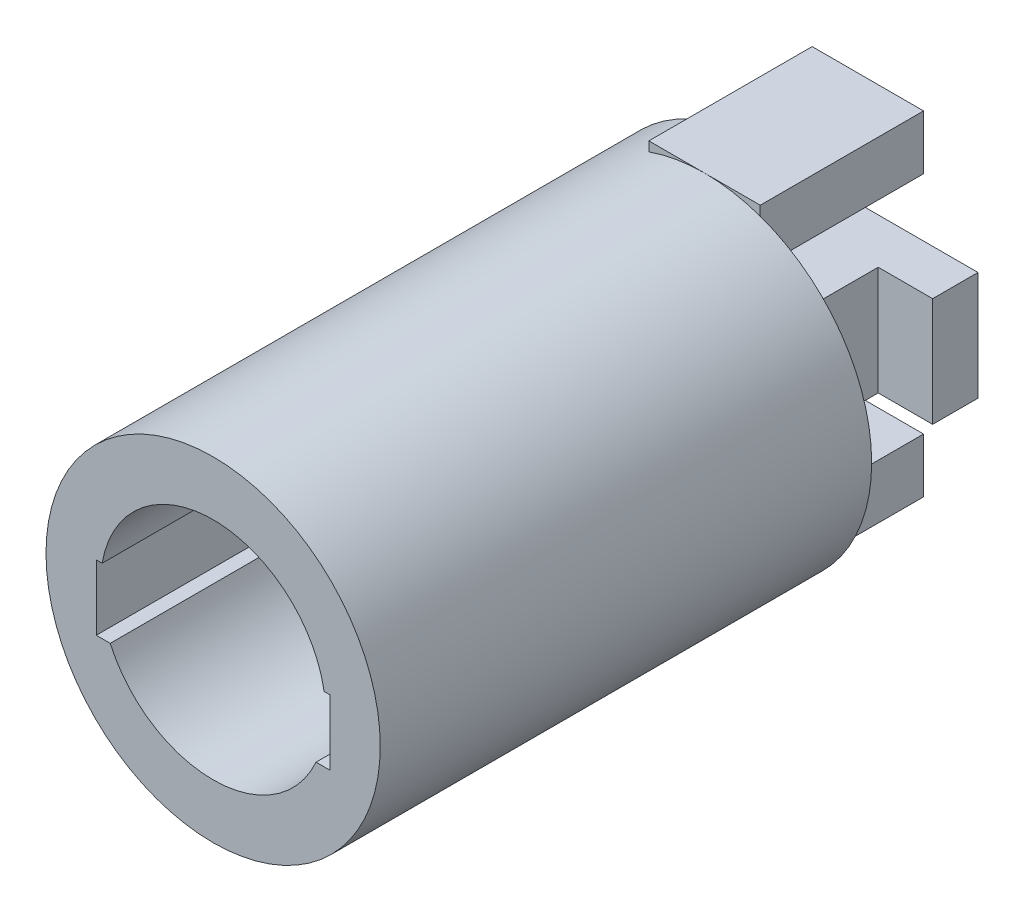
SolidWorks part; units mm, degrees
ref_plane "Front Plane" through (0, 0, 0) normal (0, 0, 1) x (1, 0, 0)
ref_plane "Top Plane" through (0, 0, 0) normal (0, 1, 0) x (1, 0, 0)
ref_plane "Right Plane" through (0, 0, 0) normal (1, 0, 0) x (0, 0, -1)
ref_plane "Plane6" through (0, 0, 0) normal (0, 0, 1) x (1, 0, 0)
sketch "Sketch9" plane through (0, 0, 0) normal (0, 0, 1) x (1, 0, 0)
  line L0 (17.9123, -8.844) -> (17.9123, 0.366)
  line L1 (21.1323, -4.604) -> (14.6923, -4.604) construction
  line L5 (14.6923, -3.704) -> (21.1323, -3.704)
  line L6 (14.6923, -3.704) -> (14.6923, -5.504)
  line L7 (14.6923, -5.504) -> (21.1323, -5.504)
  line L8 (21.1323, -3.704) -> (21.1323, -5.504)
  line L10 (17.9123, -5.504) -> (17.9123, -3.704) construction
  circle A0 centre (17.9123, -4.239) radius 4.605
  circle A1 centre (17.9123, -4.239) radius 3.105
  point P4 (0, 0)
  point P5 (0, 0)
  point P6 (17.9123, -12.5328)
  point P9 (17.9123, -4.604)
  dimension "D1" = 6.21
  dimension "D8" = 1.5
  dimension "D3" = 0.9
  dimension "D4" = 0.9
  dimension "D6" = 3.22
  dimension "D7" = 3.22
ref_plane "Plane8" through (0, 0, -13.54) normal (0, 0, 1) x (1, 0, 0)
extrude "Boss-Extrude6" add sketch "Sketch9" against normal up to surface (13.54 mm away) contours A0 A1 L5 L8 L7 L6 | A1 L5 L8 L7 L0 A0 region at (13.4102, -4.239, 0) region at (18.0152, -8.094, 0) up to plane "Plane8"
extrude "Boss-Extrude9" add sketch "Sketch9<8>" against normal blind 1.5 from surface contours A1 L0 A0 L7 L6 L5 | L7 A1 L0 | L5 A1 L7 L0 | L0 A1 L5 | A1 L5 L6 L7 region at (13.4102, -4.239, 0) region at (16.7892, -6.2627, 0) region at (16.3921, -4.5932, 0) region at (14.7986, -4.7849, 0) region at (16.6579, -2.6277, 0) starting at plane "Plane8"
sketch "Sketch9<8>" plane through (0, 0, 0) normal (0, 0, 1) x (1, 0, 0) same geometry as "Sketch9"
ref_plane "Plane10" through (0, 0, -15.04) normal (0, 0, -1) x (-1, 0, 0)
sketch "Sketch11" plane through (0, 0, -13.54) normal (0, 0, 1) x (1, 0, 0)
  line L1 (16.3773, -8.844) -> (19.4473, -8.844)
  line L2 (16.3773, -8.844) -> (16.3773, 0.366)
  line L3 (16.3773, 0.366) -> (19.4473, 0.366)
  line L4 (19.4473, -8.844) -> (19.4473, 0.366)
  line L5 (16.3773, -8.844) -> (19.4473, 0.366) construction
  line L6 (16.3773, 0.366) -> (19.4473, -8.844) construction
  line L8 (14.8773, -5.739) -> (20.9473, -5.739)
  line L9 (14.8773, -5.739) -> (14.8773, -2.739)
  line L10 (14.8773, -2.739) -> (20.9473, -2.739)
  line L11 (20.9473, -5.739) -> (20.9473, -2.739)
  line L12 (14.8773, -5.739) -> (20.9473, -2.739) construction
  line L13 (14.8773, -2.739) -> (20.9473, -5.739) construction
  line L14 (19.4473, -1.134) -> (16.3773, -1.134)
  line L15 (19.4473, -7.344) -> (16.3773, -7.344)
  arc A1 (20.9708, -3.704) -> (17.9123, -1.134) centre (17.9123, -4.239) ccw construction
  arc A2 (17.9123, -7.344) -> (20.7479, -5.504) centre (17.9123, -4.239) ccw construction
  point P0 (17.9123, -4.239)
  point P9 (17.9123, -4.239)
  dimension "D1" = 3.07
  dimension "D2" = 3
  dimension "D3" = 1.5
extrude "Boss-Extrude7" add sketch "Sketch11" against normal blind 3 and the other way blind 1.5 from surface contours L14 L4 L3 L2 | L4 L15 L2 L1 | L10 L2 L8 L4 region at (17.9123, -8.094, -13.54) region at (17.9123, -4.239, -13.54) region at (17.9123, -0.384, -13.54) starting at plane "Plane10"
ref_plane "Plane11" through (0, 0, -18.04) normal (0, 0, -1) x (-1, 0, 0)
extrude "Boss-Extrude10" add sketch "Sketch11<8>" along normal blind 1.25 from surface contours L10 L9 L8 L2 | L8 L11 L10 L4 region at (15.6273, -4.239, -13.54) region at (20.1973, -4.239, -13.54) starting at plane "Plane11"
sketch "Sketch11<8>" plane through (0, 0, -13.54) normal (0, 0, 1) x (1, 0, 0) same geometry as "Sketch11"
equation "\"D1@Boss-Extrude10\"=1.50mm-.25"
